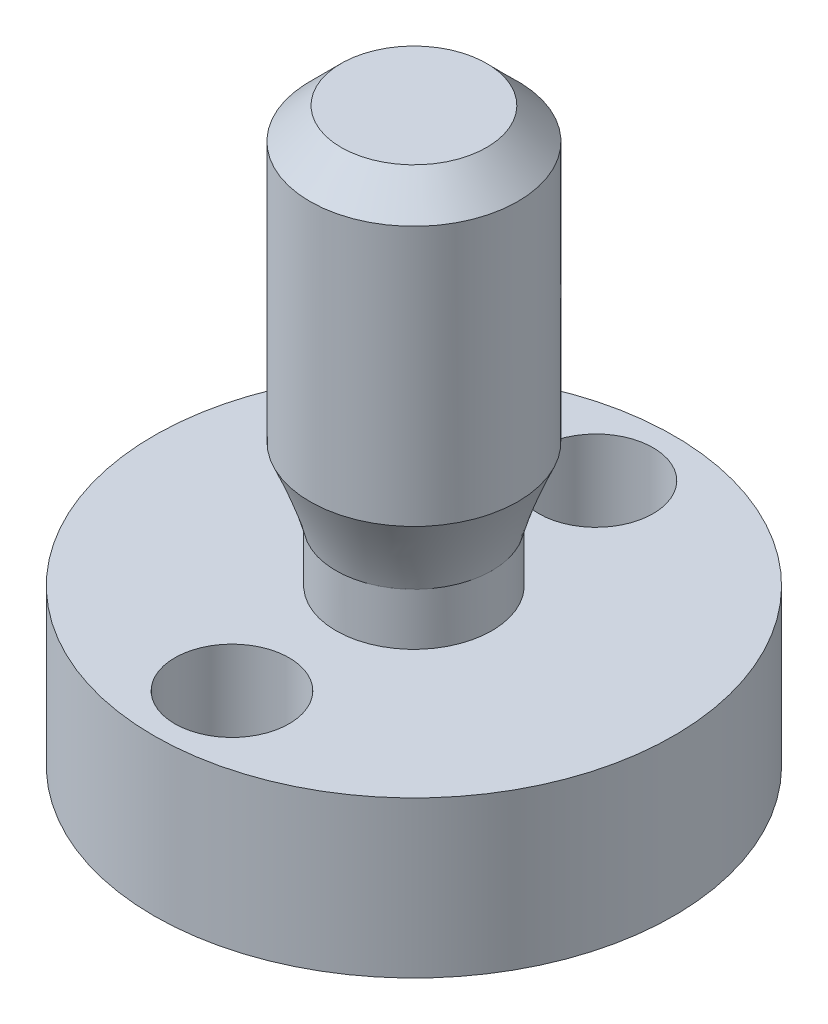
SolidWorks part; units mm, degrees
ref_plane "Front Plane" through (0, 0, 0) normal (0, 0, 1) x (1, 0, 0)
ref_plane "Top Plane" through (0, 0, 0) normal (0, 1, 0) x (1, 0, 0)
ref_plane "Right Plane" through (0, 0, 0) normal (1, 0, 0) x (0, 0, -1)
sketch "Sketch1" plane through (0, 0, 0) normal (0, 1, 0) x (1, 0, 0)
  circle A0 centre (0, 0) radius 25
  circle A1 centre (0, 0) radius 10
  circle A2 centre (0, 0) radius 7.5
  circle A3 centre (0, 17.5) radius 5.5
  circle A4 centre (0, -17.5) radius 5.5
  circle A5 centre (0, -17.5) radius 3.3
  circle A6 centre (0, 17.5) radius 3.3
  circle A7 centre (0, 0) radius 7.5
  dimension "D1" = 17.5
  dimension "D2" = 11
  dimension "D3" = 50
  dimension "D4" = 20
  dimension "D5" = 15
  dimension "D7" = 11
  dimension "D8" = 6.6
  dimension "D9" = 6.6
  dimension "D10" = 15
  dimension "D6" = 17.5
extrude "Boss-Extrude2" add sketch "Sketch1" along normal blind 15 contours A0 A4 A3 A1 | A1 A2 | A2 region at (-24.2929, 0, 0) region at (-9.7172, 0, 0) region at (0, 0, 0)
extrude "Boss-Extrude6" add sketch "Sketch1<7>" along normal blind 20 contours A2 region at (0, 0, 0)
sketch "Sketch1<7>" plane through (0, 0, 0) normal (0, 1, 0) x (1, 0, 0) same geometry as "Sketch1"
extrude "Boss-Extrude9" add sketch "Sketch1<9>" along normal blind 5 contours A3 A6 region at (-5.3444, 0, -17.5)
sketch "Sketch1<9>" plane through (0, 0, 0) normal (0, 1, 0) x (1, 0, 0) same geometry as "Sketch1"
extrude "Boss-Extrude10" add sketch "Sketch1<10>" along normal blind 5 contours A4 A5 region at (-5.3444, 0, 17.5)
sketch "Sketch1<10>" plane through (0, 0, 0) normal (0, 1, 0) x (1, 0, 0) same geometry as "Sketch1"
extrude "Boss-Extrude11" add sketch "Sketch1<11>" against normal blind 2 contours A2 A7 | A7 region at (-9.7172, 0, 0) region at (0, 0, 0)
sketch "Sketch1<11>" plane through (0, 0, 0) normal (0, 1, 0) x (1, 0, 0) same geometry as "Sketch1"
ref_plane "Plane5" through (0, 27, 0) normal (0, 1, 0) x (1, 0, 0)
sketch "Sketch16" plane through (0, 27, 0) normal (0, 1, 0) x (1, 0, 0)
  circle A0 centre (0, 0) radius 10
  dimension "D1" = 20
extrude "Boss-Extrude15" add sketch "Sketch16" along normal blind 28 separate body
loft "Loft1" add section edge at (0, 27, 10) section edge at (0, 20, 7.5) connector at (-8.6042, 27, -5.0958) connector at (-4.5107, 20, -5.992)
chamfer "Chamfer12" distance 3 angle 45 1 edges at (0, 55, 10)
sketch "Sketch17" plane through (0, -2, 0) normal (0, -1, 0) x (1, 0, 0)
  circle A0 centre (0, 0) radius 7.5
extrude "Cut-Extrude1" cut sketch "Sketch17" against normal blind 2 flip side to cut
